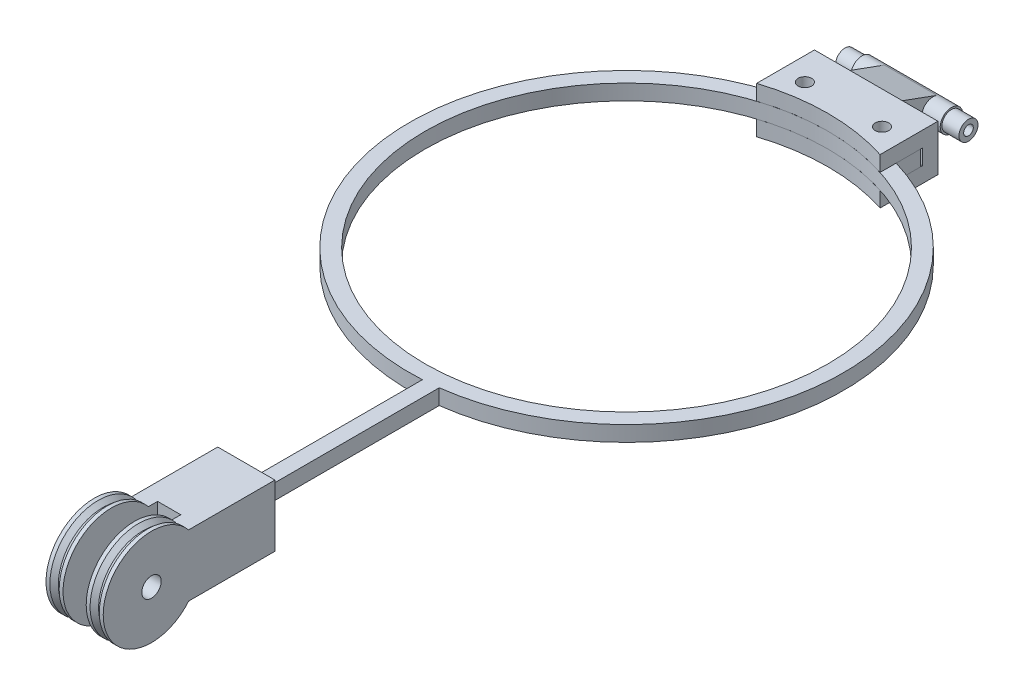
SolidWorks part; units mm, degrees
ref_plane "Front Plane" through (0, 0, 0) normal (0, 0, 1) x (1, 0, 0)
ref_plane "Top Plane" through (0, 0, 0) normal (0, 1, 0) x (1, 0, 0)
ref_plane "Right Plane" through (0, 0, 0) normal (1, 0, 0) x (0, 0, -1)
sketch "Sketch1" plane through (0, 0, 0) normal (0, 0, 1) x (1, 0, 0)
  line L0 (0, 0) -> (11.6505, 0) construction
  line L1 (0, 4) -> (7, 4)
  line L2 (0, 0) -> (0, 4) construction
  line L3 (0, 4) -> (0, 19.875)
  line L6 (7, 19.875) -> (7, 4)
  line L7 (3.5, 4) -> (3.5, 18.2875) construction
  line L8 (0, 19.875) -> (1.5875, 19.875)
  line L9 (1.5875, 19.875) -> (3.5, 18.2875)
  line L10 (5.4125, 19.875) -> (3.5, 18.2875)
  line L11 (7, 19.875) -> (5.4125, 19.875)
  dimension "D1" = 7
  dimension "D2" = 8
  dimension "D3" = 1.5875
  dimension "D4" = 15.875
  dimension "D5" = 1.5875
revolve "Revolve1" add sketch "Sketch1" angle 360 about L0
sketch "Sketch2" plane through (7, 0, 0) normal (1, 0, 0) x (0, 0, -1)
  line L0 (0, 0) -> (50.8, 0) construction
  line L1 (14.196, 12.7) -> (50.8, 12.7)
  line L2 (50.8, 12.7) -> (50.8, 0)
  line L3 (14.196, -12.7) -> (50.8, -12.7)
  line L4 (50.8, -12.7) -> (50.8, 0)
  circle A0 centre (0, 0) radius 4 construction
  circle A1 centre (0, 0) radius 4
  arc A7 (12.4648, 13.3814) -> (12.4648, -13.3814) centre (0, 0) ccw
  arc A8 (14.196, -12.7) -> (12.4648, -13.3814) centre (14.196, -15.24) ccw
  arc A9 (14.196, 12.7) -> (12.4648, 13.3814) centre (14.196, 15.24) cw
  circle A10 centre (0, 0) radius 18.2875 construction
  dimension "D3" = 2.54
  dimension "D1" = 50.8
  dimension "D2" = 25.4
extrude "Boss-Extrude1" add sketch "Sketch2" against normal up to surface (7 mm away) up to face at (0, 0, 4)
move or copy body "Body-Move/Copy1" bodies to move or copy 102 copy yes number of copies 1 translate (16.54, 0, 0) parameters "D1"=16.54, "D2"=0, "D3"=0
sketch "Sketch10" plane through (0, 12.7, 0) normal (0, 1, 0) x (1, 0, 0)
  line L1 (23.54, 50.8) -> (0, 50.8)
  line L2 (23.54, 50.8) -> (23.54, 19.05)
  line L3 (23.54, 19.05) -> (0, 19.05)
  line L4 (0, 50.8) -> (0, 19.05)
  line L5 (0, 15.2881) -> (0, 50.8) construction
  dimension "D1" = 31.75
extrude "Boss-Extrude7" add sketch "Sketch10" against normal up to surface (25.4 mm away) up to face at (3.3754, -12.7, -23.8931)
sketch "Sketch11" plane through (0, 0, -50.8) normal (0, 0, -1) x (-1, 0, 0)
  line L0 (-11.77, 12.7) -> (-11.77, -12.7) construction
  line L1 (-15.326, 3.556) -> (-8.214, 3.556)
  line L2 (-15.326, 3.556) -> (-15.326, -3.556)
  line L3 (-15.326, -3.556) -> (-8.214, -3.556)
  line L4 (-8.214, 3.556) -> (-8.214, -3.556)
  line L5 (0, 12.7) -> (-23.54, 12.7) construction
  line L6 (0, -12.7) -> (-23.54, -12.7) construction
  line L7 (-15.326, -3.556) -> (-8.214, 3.556) construction
  point P10 (-11.77, 0)
  point P11 (0, 0)
  dimension "D1" = 7.112
extrude "Cut-Extrude2" cut sketch "Sketch11" against normal offset from surface (28.575 mm away) 3.175 up to face at (11.77, 0, -19.05)
sketch "Sketch12" plane through (0, 0, -22.225) normal (0, 0, -1) x (-1, 0, 0)
  line L0 (-15.326, 3.556) -> (-8.214, -3.556) construction
  line L1 (-14.945, -3.175) -> (-8.595, 3.175) construction
  line L2 (-14.945, -3.175) -> (-8.595, -3.175)
  line L3 (-14.945, -3.175) -> (-14.945, 3.175)
  line L4 (-14.945, 3.175) -> (-8.595, 3.175)
  line L5 (-8.595, -3.175) -> (-8.595, 3.175)
  point P4 (-11.77, 0)
  point P5 (0, 0)
  dimension "D1" = 6.35
extrude "Boss-Extrude8" add sketch "Sketch12" along normal offset from surface (104.775 mm away) 76.2 separate body up to face at (11.77, 0, -50.8) offset beyond the face yes
sketch "Sketch13" plane through (0, 3.175, 0) normal (0, 1, 0) x (1, 0, 0)
  line L0 (3.5, 0) -> (3.5, 304.8) construction
  line L2 (23.54, -4) -> (23.54, 4) construction
  line L3 (-78.014, 304.8) -> (112.9554, 304.8) construction
  line L5 (23.54, -4) -> (23.54, 4)
  line L6 (23.54, 0) -> (3.5, 0) construction
  line L7 (-21.9, 301.1101) -> (-21.9, 311.15)
  line L8 (-21.9, 311.15) -> (28.9, 311.15)
  line L9 (28.9, 311.15) -> (28.9, 301.1101)
  line L10 (3.5, -18.2875) -> (3.5, 12.4648) construction
  arc A0 (-21.9, 301.1101) -> (28.9, 301.1101) centre (3.5, 215.5316) ccw
  circle A1 centre (3.5, 215.5316) radius 82.9184
  circle A2 centre (-12.375, 304.8) radius 2.7781
  circle A3 centre (19.375, 304.8) radius 2.7781
  circle A4 centre (3.5, 215.5316) radius 89.2684 construction
  point P2 (3.5, 0)
  point P22 (-1.8368, 304.8)
  line M5 (14.945, 127) -> (8.595, 127)
  line M8 (14.945, 22.225) -> (14.945, 127)
  dimension "D5" = 5.5562
  dimension "D1" = 304.8
  dimension "D3" = 50.8
  dimension "D4" = 6.35
  dimension "D6" = 9.525
  dimension "D2" = 6.35
extrude "Boss-Extrude9" add sketch "Sketch13" against normal up to surface (6.35 mm away) contours A0 A1 M8 M5 region at (-19.3298, 3.175, -306.1301) up to face at (11.77, -3.175, -74.6125)
sketch "Sketch14" plane through (0, 3.175, 0) normal (0, 1, 0) x (1, 0, 0)
  line L0 (-21.9, 294.4639) -> (-21.9, 318.262)
  line L1 (-21.9, 318.262) -> (28.9, 318.262)
  line L2 (28.9, 318.262) -> (28.9, 294.4639)
  line L3 (28.9, 311.15) -> (28.9, 301.1101) construction
  line L4 (-21.9, 301.1101) -> (-21.9, 311.15) construction
  line L5 (-21.9, 311.15) -> (28.9, 311.15) construction
  arc A0 (-21.9, 294.4639) -> (28.9, 294.4639) centre (3.5, 215.5316) cw
  circle A1 centre (3.5, 215.5316) radius 82.9184 construction
  circle A2 centre (19.375, 304.8) radius 2.7781 construction
  circle A3 centre (-12.375, 304.8) radius 2.7781 construction
  circle A4 centre (19.375, 304.8) radius 2.7781
  circle A5 centre (-12.375, 304.8) radius 2.7781
  dimension "D1" = 7.112
extrude "Boss-Extrude10" add sketch "Sketch14" along normal blind 6.35 separate body
sketch "Sketch15" plane through (0, 3.175, 0) normal (0, -1, 0) x (1, 0, 0)
  line L0 (28.9, -294.4639) -> (28.9, -318.262) construction
  line L1 (-21.9, -318.262) -> (28.9, -318.262)
  line L2 (-21.9, -318.262) -> (-21.9, -311.912)
  line L3 (-21.9, -311.912) -> (28.9, -311.912)
  line L4 (28.9, -318.262) -> (28.9, -311.912)
  dimension "D1" = 6.35
extrude "Boss-Extrude11" add sketch "Sketch15" along normal blind 3.175
mirror "Mirror1" about plane through (0, 0, 0) normal (0, 1, 0) of bodies 118
combine bodies "Combine2" operation type add bodies to combine 118 119
ref_plane "Plane2" through (3.5, 0, 0) normal (-1, 0, 0) x (0, 0, 1)
sketch "Sketch17" plane through (3.5, 0, 0) normal (-1, 0, 0) x (0, 0, 1)
  line L0 (-319.8495, 5.4291) -> (-319.8495, -3.6613) construction
  line L1 (-318.262, 9.525) -> (-318.262, -9.525) construction
  line L2 (-332.4378, 4.3544) -> (-318.262, 9.525)
  line L3 (-318.262, -9.525) -> (-332.4378, -4.3544)
  line L4 (-318.262, 9.525) -> (-318.262, -9.525)
  circle A0 centre (-330.8495, 0) radius 11 construction
  circle A1 centre (-330.8495, 0) radius 4 construction
  circle A2 centre (-330.8495, 0) radius 3.9238
  circle A5 centre (-330.8495, 0) radius 1.9844
  circle A6 centre (-330.8495, 0) radius 4.635
  point P5 (0, 0)
  point P17 (0, 0)
  point P20 (-332.4201, 5.4291)
  point P21 (-332.4474, -4.6438)
  dimension "D1" = 22
  dimension "D2" = 8
  dimension "D6" = 3.9688
  dimension "D4" = 9.27
  dimension "D5" = 1.5875
  dimension "D3" = 0.0762
extrude "Boss-Extrude12" add sketch "Sketch17" along normal mid plane 21.59 separate body contours A6 L3 L4 L2 | A2 region at (3.5, 0, -322.7715)
extrude "Boss-Extrude13" add sketch "Sketch17<3>" along normal mid plane 50.8 contours A2 A5 region at (3.5, 0, -334.6623)
sketch "Sketch17<3>" plane through (3.5, 0, 0) normal (-1, 0, 0) x (0, 0, 1) same geometry as "Sketch17"
extrude "Boss-Extrude14" add sketch "Sketch17<5>" along normal mid plane 36.8 contours A6 A2 region at (3.5, 3.6903, -328.2674)
sketch "Sketch17<5>" plane through (3.5, 0, 0) normal (-1, 0, 0) x (0, 0, 1) same geometry as "Sketch17"
